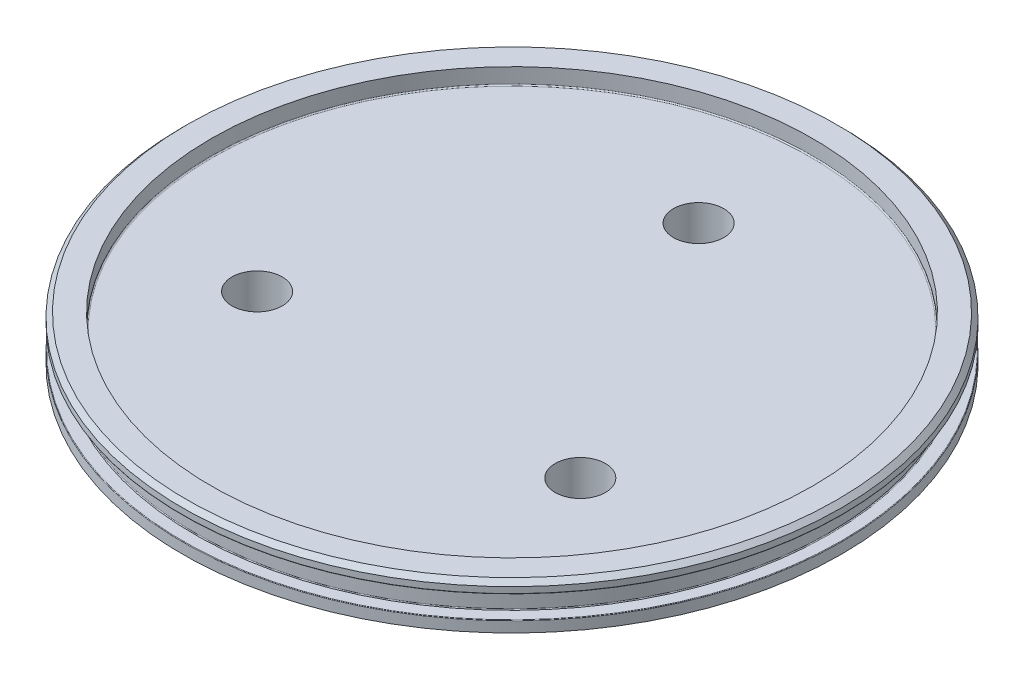
SolidWorks part; units mm, degrees
material "6061-T6 (SS)"
ref_plane "Front Plane" through (0, 0, 0) normal (0, 0, 1) x (1, 0, 0)
ref_plane "Top Plane" through (0, 0, 0) normal (0, 1, 0) x (1, 0, 0)
ref_plane "Right Plane" through (0, 0, 0) normal (1, 0, 0) x (0, 0, -1)
sketch "Sketch1" plane through (0, 0, 0) normal (0, 0, 1) x (1, 0, 0)
  line L0 (0, 48.1922) -> (0, -25.6743) construction
  line L1 (0, 0) -> (72.898, 0)
  line L2 (72.898, 0) -> (72.898, 2.4638)
  line L3 (72.898, 2.4638) -> (70.0532, 2.4638)
  line L4 (70.0532, 2.4638) -> (70.0532, 7.4422)
  line L5 (70.0532, 7.4422) -> (72.898, 7.4422)
  line L6 (72.898, 7.4422) -> (72.898, 9.906)
  line L7 (72.898, 9.906) -> (66.548, 9.906)
  line L8 (66.548, 9.906) -> (66.548, 6.35)
  line L9 (66.548, 6.35) -> (0, 6.35)
  line L10 (0, 6.35) -> (0, 0)
  dimension "D1" = 145.796
  dimension "D2" = 4.9784
  dimension "D3" = 2.8448
  dimension "D4" = 9.906
  dimension "D5" = 6.35
  dimension "D6" = 6.35
revolve "Revolve1" add sketch "Sketch1" angle 360 about L0
sketch "Sketch6" plane through (0, 0, 0) normal (0, -1, 0) x (1, 0, 0)
  circle A0 centre (0, 0) radius 66.04
  dimension "D1" = 132.08
extrude "Boss-Extrude1" add sketch "Sketch6" along normal blind 2.54
hole_wizard "Pipe Tap Drill for 1/4 Tap - GN2" positions "Sketch2" profile "Sketch3" hole size "1/4" standard "ANSI Inch" end condition through all
sketch "Sketch2" plane through (0, 6.35, 0) normal (0, 1, 0) x (1, 0, 0)
  line L0 (-35.7452, -20.6375) -> (35.7452, -20.6375) construction
  line L1 (35.7452, -20.6375) -> (0, 41.275) construction
  line L2 (0, 41.275) -> (-35.7452, -20.6375) construction
  circle A0 centre (0, 0) radius 41.275 construction
  point P41 (-35.7452, -20.6375)
  point P44 (0, 41.275)
  point P47 (35.7452, -20.6375)
  dimension "D1" = 82.55
sketch "Sketch3" plane through (35.7452, 6.35, 20.6375) normal (1, 0, 0) x (0, 0, 1)
  line L0 (0, 0) -> (0, 8.89)
  line L1 (0, 8.89) -> (5.5626, 8.89)
  line L2 (5.5626, 8.89) -> (5.5626, 0)
  line L5 (5.5626, 0) -> (0, 0)
  line L11 (0, -6.35) -> (0, 107.95) construction
  dimension "Thru Hole Dia." = 11.1252
  dimension "Thru Hole Depth" = 8.89
fillet "CNC ID Fillet" radius 0.1778 3 edges at (-70.0532, 7.4422, 0) (-70.0532, 2.4638, 0) (66.04, 0, 0)
fillet "CNC OD Fillet" radius 0.127 3 edges at (-72.898, 7.4422, 0) (-72.898, 2.4638, 0) (66.04, -2.54, 0)
chamfer "CNC Chamfers" distance 1.016 angle 45 1 edges at (-72.898, 9.906, 0)
fillet "CNC Bore Fillet" radius 0.254 1 edges at (-66.548, 6.35, 0)
